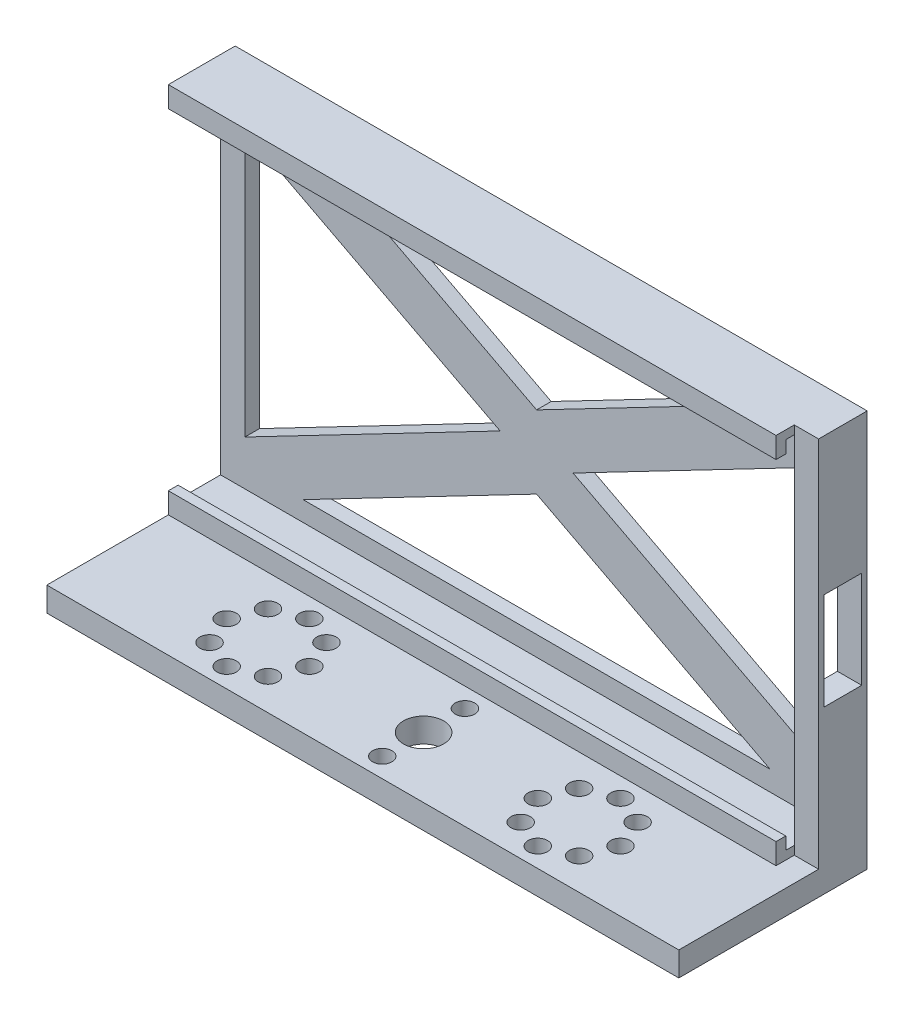
SolidWorks part; units mm, degrees
ref_plane "Front Plane" through (0, 0, 0) normal (0, 0, 1) x (1, 0, 0)
ref_plane "Top Plane" through (0, 0, 0) normal (0, 1, 0) x (1, 0, 0)
ref_plane "Right Plane" through (0, 0, 0) normal (1, 0, 0) x (0, 0, -1)
sketch "Sketch1" plane through (0, 0, 0) normal (0, 0, 1) x (1, 0, 0)
  line L0 (65, 38.325) -> (65, 34.025)
  line L1 (-65, 38.325) -> (65, 38.325)
  line L2 (-65, 38.325) -> (-65, -38.325)
  line L3 (-65, -38.325) -> (65, -38.325)
  line L4 (65, 38.325) -> (65, -38.325)
  line L5 (-65, 38.325) -> (65, -38.325) construction
  line L6 (-65, -38.325) -> (65, 38.325) construction
  line L7 (-65, 36.575) -> (65, 36.575)
  line L8 (-65, 36.575) -> (-65, -36.575)
  line L9 (-65, -36.575) -> (65, -36.575)
  line L10 (65, 36.575) -> (65, -36.575)
  line L11 (-65, 36.575) -> (65, -36.575) construction
  line L12 (-65, -36.575) -> (65, 36.575) construction
  line L13 (65, 34.025) -> (-65, 34.025)
  line L14 (0, 7.5) -> (-48.0246, 32.5)
  line L15 (60, 32.5) -> (-60, 32.5)
  line L16 (60, 32.5) -> (60, -32.5)
  line L17 (60, -32.5) -> (-60, -32.5)
  line L18 (-60, 32.5) -> (-60, -32.5)
  line L19 (60, 32.5) -> (-60, -32.5) construction
  line L20 (60, -32.5) -> (-60, 32.5) construction
  line L21 (-7.5, 0) -> (-60, 27.3298)
  line L22 (48.0246, 32.5) -> (0, 7.5)
  line L23 (7.5, 0) -> (60, 27.3298)
  line L24 (0, 7.5) -> (0, 32.5)
  line L25 (7.5, 0) -> (-7.5, 0)
  line L26 (0, -7.5) -> (-48.0246, -32.5)
  line L27 (-7.5, 0) -> (-60, -27.3298)
  line L28 (7.5, 0) -> (60, -27.3298)
  line L29 (48.0246, -32.5) -> (0, -7.5)
  line L30 (65, -38.325) -> (65, -43.325)
  line L31 (65, -43.325) -> (-65, -43.325)
  line L32 (-65, -43.325) -> (-65, -38.325)
  line L33 (65, -34.025) -> (-65, -34.025)
  line L34 (60, 32.5) -> (60, 38.325)
  line L35 (65, -34.025) -> (65, -38.325)
  line L36 (60, -32.5) -> (60, -38.325)
  circle A0 centre (0, 0) radius 7.5
  point P0 (0, 0)
  point P6 (0, 0)
  dimension "D6" = 15
  dimension "D1" = 76.65
  dimension "D2" = 73.15
  dimension "D3" = 130
  dimension "D4" = 130
  dimension "D5" = 4.3
  dimension "D7" = 65
  dimension "D8" = 120
  dimension "D9" = 62.5
  dimension "D10" = 62.5
  dimension "D11" = 5
extrude "Boss-Extrude1" add sketch "Sketch1" along normal blind 38.75 contours L32 L31 L30 L3 region at (0, -40.825, 0)
extrude "Boss-Extrude2" add sketch "Sketch1<4>" along normal blind 3 separate body contours A0 L23 L16 L15 L22 | A0 L14 L15 L18 L21 | A0 L29 L17 L16 L28 | L25 A0 | L25 A0 | A0 L27 L18 L17 L26 | L13 L4 L7 L2 | L10 L33 L2 L9 | L36 L17 L18 L15 L34 L13 L8 L33 region at (-2.5, 35.3, 0) region at (58.5768, 33.2625, 0) region at (-2.5, -35.3, 0) region at (31.0483, 17.8606, 0) region at (31.0483, -17.8606, 0) region at (-31.0483, 17.8606, 0) region at (0, 3.1831, 0) region at (0, -3.1831, 0) region at (-31.0483, -17.8606, 0)
sketch "Sketch1<4>" plane through (0, 0, 0) normal (0, 0, 1) x (1, 0, 0) same geometry as "Sketch1"
extrude "Boss-Extrude3" add sketch "Sketch1<5>" along normal blind 11.75 contours L9 L2 L3 L4 | L2 L7 L0 L1 region at (-2.5, 37.45, 0) region at (-2.5, -37.45, 0)
sketch "Sketch1<5>" plane through (0, 0, 0) normal (0, 0, 1) x (1, 0, 0) same geometry as "Sketch1"
extrude "Boss-Extrude5" add sketch "Sketch1<7>" along normal blind 2 from offset 11.75 contours L2 L7 L0 L1 | L13 L4 L7 L2 | L10 L33 L2 L9 | L9 L2 L3 L4 region at (-2.5, 37.45, 0) region at (-2.5, 35.3, 0) region at (-2.5, -35.3, 0) region at (-2.5, -37.45, 0)
sketch "Sketch1<7>" plane through (0, 0, 0) normal (0, 0, 1) x (1, 0, 0) same geometry as "Sketch1"
sketch "Sketch2" plane through (0, -43.325, 0) normal (0, -1, 0) x (1, 0, 0)
  line L0 (65, 38.75) -> (-65, 38.75)
  line L1 (-65, 38.75) -> (-65, 13.75)
  line L2 (-65, 38.75) -> (-65, 0) construction
  line L3 (-65, 13.75) -> (65, 13.75)
  line L4 (65, 38.75) -> (65, 0) construction
  line L5 (65, 13.75) -> (65, 38.75)
  line L6 (0, 13.75) -> (0, 38.75)
  line L7 (0, 26.25) -> (32, 26.25)
  line L8 (32, 26.25) -> (32, 34.75)
  line L9 (0, 26.25) -> (0, 34.75)
  circle A0 centre (0, 26.25) radius 4.1242
  circle A1 centre (32, 34.75) radius 2
  circle A2 centre (38.0104, 32.2604) radius 2
  circle A3 centre (40.5, 26.25) radius 2
  circle A4 centre (38.0104, 20.2396) radius 2
  circle A5 centre (32, 17.75) radius 2
  circle A6 centre (25.9896, 20.2396) radius 2
  circle A7 centre (23.5, 26.25) radius 2
  circle A8 centre (25.9896, 32.2604) radius 2
  circle A9 centre (-38.0104, 20.2396) radius 2
  circle A10 centre (-32, 17.75) radius 2
  circle A11 centre (-25.9896, 20.2396) radius 2
  circle A12 centre (-23.5, 26.25) radius 2
  circle A13 centre (-25.9896, 32.2604) radius 2
  circle A14 centre (-32, 34.75) radius 2
  circle A15 centre (-38.0104, 32.2604) radius 2
  circle A16 centre (-40.5, 26.25) radius 2
  circle A17 centre (0, 34.75) radius 2
  circle A18 centre (0, 17.75) radius 2
  point P33 (32, 26.25)
  dimension "D4" = 4
  dimension "D6" = 4
  dimension "D1" = 25
  dimension "D2" = 32
  dimension "D3" = 8.5
  dimension "D7" = 8.5
  dimension "D5" = 8
extrude "Cut-Extrude1" cut sketch "Sketch2" against normal blind 13.75 contours A14 | A15 | A16 | A9 | A10 | A11 | A12 | A13 | A8 | L7 A7 | L7 A7 | A6 | A5 | A1 | A2 | A3 | A4 | L6 A0 | L6 A0 L7 | L7 A0 L6 | L6 A17 | L6 A17 | A18 region at (30.6258, -43.325, 36.1242) region at (23.5, -43.325, 27.0988) region at (23.5, -43.325, 25.4012) region at (0.8488, -43.325, 34.75) region at (-0.8488, -43.325, 34.75) region at (1.7504, -43.325, 28.0004) region at (-1.7504, -43.325, 26.25) region at (1.7504, -43.325, 24.4996) region at (38.0104, -43.325, 32.2604) region at (40.5, -43.325, 26.25) region at (38.0104, -43.325, 20.2396) region at (32, -43.325, 17.75) region at (25.9896, -43.325, 20.2396) region at (25.9896, -43.325, 32.2604) region at (-38.0104, -43.325, 20.2396) region at (-32, -43.325, 17.75) region at (-25.9896, -43.325, 20.2396) region at (-23.5, -43.325, 26.25) region at (-25.9896, -43.325, 32.2604) region at (-32, -43.325, 34.75) region at (-38.0104, -43.325, 32.2604) region at (-40.5, -43.325, 26.25)
extrude "Boss-Extrude7" add sketch "Sketch1<9>" along normal blind 10 contours L16 L36 L33 L4 L13 L34 | L33 L36 L9 L10 | L9 L36 L3 L4 | L34 L13 L4 L7 | L34 L7 L0 L1 region at (62.5, 37.45, 0) region at (62.5, 35.3, 0) region at (62.5, 0, 0) region at (62.5, -35.3, 0) region at (62.5, -37.45, 0)
sketch "Sketch1<9>" plane through (0, 0, 0) normal (0, 0, 1) x (1, 0, 0) same geometry as "Sketch1"
sketch "Sketch3" plane through (65, 0, 0) normal (1, 0, 0) x (0, 0, -1)
  line L0 (0, -43.325) -> (0, 38.325)
  line L1 (0, 38.325) -> (-10, 38.325)
  line L2 (-10, 38.325) -> (-10, -43.325)
  line L3 (-38.75, -43.325) -> (0, -43.325) construction
  line L4 (-10, -43.325) -> (0, -43.325)
  line L5 (-10, 0) -> (0, 0)
  line L6 (-10, 38.325) -> (-10, -38.325) construction
  line L8 (-8.875, 10) -> (-1.125, 10)
  line L9 (-8.875, 10) -> (-8.875, -10)
  line L10 (-8.875, -10) -> (-1.125, -10)
  line L11 (-1.125, 10) -> (-1.125, -10)
  line L12 (-8.875, 10) -> (-1.125, -10) construction
  line L13 (-8.875, -10) -> (-1.125, 10) construction
  point P14 (-5, 0)
  dimension "D1" = 7.75
  dimension "D2" = 20
extrude "Cut-Extrude2" cut sketch "Sketch3" against normal blind 10 contours L11 L8 L9 L5 | L11 L5 L9 L10 region at (65, -5, 5) region at (65, 5, 5)
